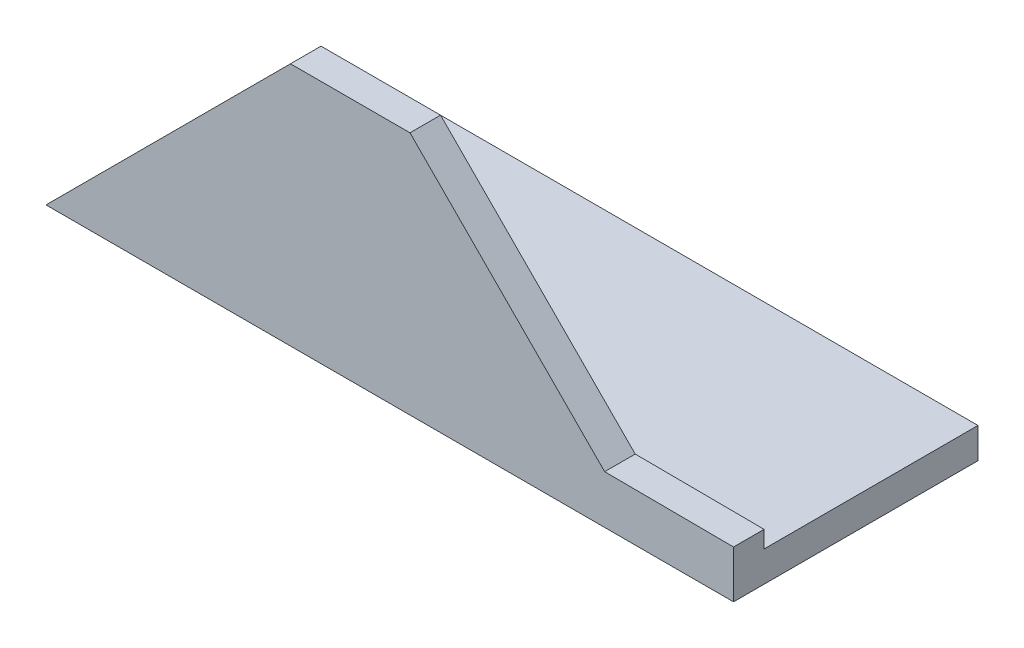
SolidWorks part; units mm, degrees
ref_plane "Спереди" through (0, 0, 0) normal (0, 0, 1) x (1, 0, 0)
ref_plane "Сверху" through (0, 0, 0) normal (0, 1, 0) x (1, 0, 0)
ref_plane "Справа" through (0, 0, 0) normal (1, 0, 0) x (0, 0, -1)
sketch "Эскиз1" plane through (0, 0, 0) normal (1, 0, 0) x (0, 0, -1)
  line L0 (0, 0) -> (32, 0)
  line L1 (0, 0) -> (0, 32)
extrude "Вытянуть-Тонкостенный1" add sketch "Эскиз1" along normal blind 90 thin thin type one direction wall 4
sketch "Эскиз2" plane through (0, 0, 0) normal (0, 0, 1) x (1, 0, 0)
  line L0 (0, 0) -> (0, 32)
  line L1 (0, 32) -> (32, 32)
  line L2 (90, 32) -> (0, 32) construction
  line L3 (32, 32) -> (0, 0)
  line L4 (90, 6.2217) -> (73.1303, 6.3232)
  line L5 (47.6477, 32) -> (90, 32)
  line L6 (90, 32) -> (90, 6.2217)
  line L9 (73.1303, 6.3232) -> (47.6477, 32)
extrude "Вырез-Вытянуть1" cut sketch "Эскиз2" against normal through all
